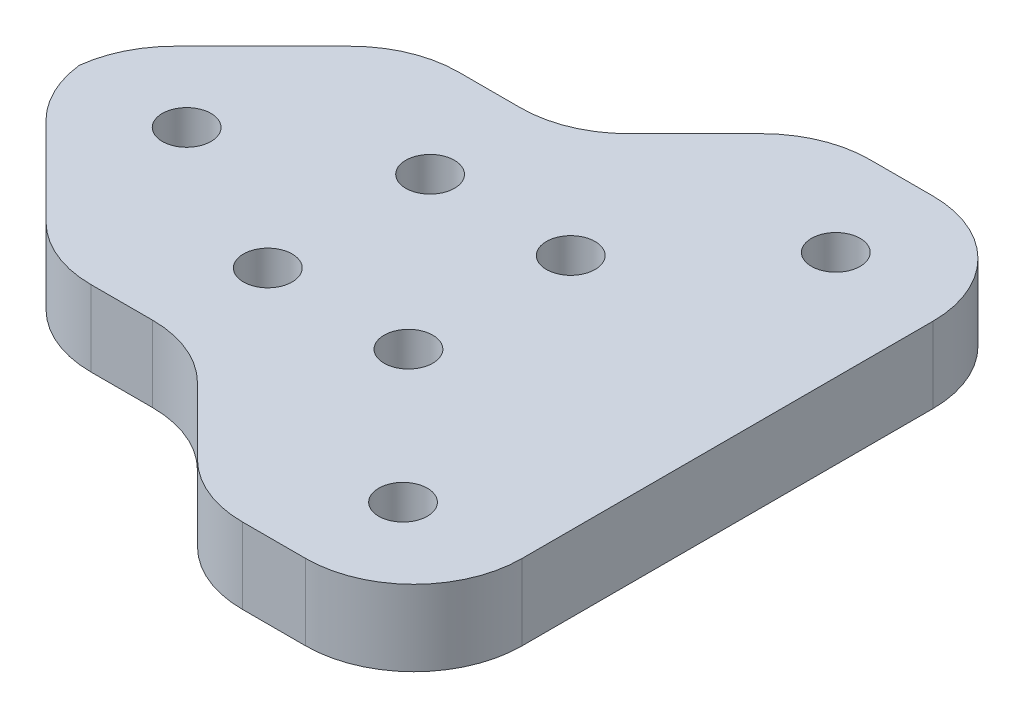
SolidWorks part; units mm, degrees
material "ABS"
ref_plane "Front Plane" through (0, 0, 0) normal (0, 0, 1) x (1, 0, 0)
ref_plane "Top Plane" through (0, 0, 0) normal (0, 1, 0) x (1, 0, 0)
ref_plane "Right Plane" through (0, 0, 0) normal (1, 0, 0) x (0, 0, -1)
sketch "Sketch1" plane through (0, 0, 0) normal (0, 1, 0) x (1, 0, 0)
  line L1 (0, 0) -> (60, 0)
  line L2 (0, 0) -> (0, 58)
  line L3 (0, 58) -> (60, 58)
  line L4 (60, 0) -> (60, 58)
  dimension "D1" = 58
  dimension "D2" = 60
extrude "Boss-Extrude1" add sketch "Sketch1" along normal blind 7
sketch "Sketch2" plane through (0, 0, 0) normal (0, 1, 0) x (1, 0, 0)
  line L0 (0, 58) -> (0, 0) construction
  line L1 (0, 7) -> (60, 7)
  line L2 (0, 7) -> (0, 0)
  line L3 (0, 0) -> (60, 0)
  line L4 (60, 7) -> (60, 0)
  dimension "D1" = 7
extrude "Boss-Extrude2" [suppressed] add sketch "Sketch2" against normal blind 20
hole_wizard "M4 Clearance Slot1" [suppressed] positions "Sketch3" profile "Sketch4" size "M4" standard "ANSI Metric"
sketch "Sketch3" plane through (0, 7, 0) normal (0, 1, 0) x (1, 0, 0)
  line L0 (32.05, 70) -> (32.05, 7) construction
  line L1 (64.1, 70) -> (0, 70) construction
  line L4 (16.235, 62.5) -> (47.865, 62.5) construction
  line L5 (47.865, 62.5) -> (47.865, 14.5) construction
  line L6 (47.865, 14.5) -> (16.235, 14.5) construction
  line L7 (16.235, 14.5) -> (16.235, 62.5) construction
  line L18 (40.365, 62.5) -> (55.365, 62.5) construction
  point P2 (47.865, 62.5)
  point P4 (47.865, 14.5)
  point P24 (16.235, 38.5)
  point P26 (32.05, 62.5)
  dimension "D1" = 31.63
  dimension "D2" = 48
  dimension "D3" = 15
  dimension "D4" = 31.5
sketch "Sketch4" plane through (47.865, 7, -62.5) normal (1, 0, 0) x (0, 0, 1)
  line L0 (0, 0) -> (0, 7)
  line L1 (0, 7) -> (2.25, 7)
  line L2 (2.25, 7) -> (2.25, 0)
  line L5 (2.25, 0) -> (0, 0)
  line L11 (0, -6.35) -> (0, 107.95) construction
  dimension "Thru Hole Dia." = 4.5
  dimension "Thru Hole Depth" = 7
hole_wizard "M2 Clearance Hole1" [suppressed] positions "Sketch8" profile "Sketch9" hole size "M2" standard "ANSI Metric"
sketch "Sketch8" plane through (0, 0, 0) normal (-1, 0, 0) x (0, 0, 1)
  line L4 (-29.5, 3.5) -> (-47.5, 3.5) construction
  line L7 (-70, 7) -> (-70, 0) construction
  point P0 (-47.5, 3.5)
  point P2 (-29.5, 3.5)
  point P23 (-70, 3.5)
  point P25 (-38.5, 3.5)
  dimension "D1" = 18
  dimension "D2" = 31.5
sketch "Sketch9" plane through (0, 3.5, -47.5) normal (0, 1, 0) x (0, 0, 1)
  line L0 (0, 0) -> (0, 35.721)
  line L1 (0, 35.721) -> (1.2, 35)
  line L2 (1.2, 35) -> (1.2, 0)
  line L5 (1.2, 0) -> (0, 0)
  line L10 (0, 35.721) -> (-1.2, 35) construction
  line L11 (0, -6.35) -> (0, 107.95) construction
  dimension "Hole Dia." = 2.4
  dimension "Hole Depth" = 35
  dimension "Drill Angle" = 118
sketch "Sketch11" plane through (0, 7, 0) normal (0, 1, 0) x (1, 0, 0)
  line L0 (0, 46) -> (28, 46)
  line L1 (0, 58) -> (0, 0) construction
  line L2 (28, 46) -> (40, 58)
  line L3 (60, 58) -> (0, 58) construction
  line L4 (0, 46) -> (0, 58)
  line L5 (0, 58) -> (40, 58)
  dimension "D1" = 135
  dimension "D2" = 12
  dimension "D3" = 40
extrude "Cut-Extrude2" [suppressed] cut sketch "Sketch11" against normal through all
sketch "Sketch12" [suppressed] plane through (0, 7, 0) normal (0, 1, 0) x (1, 0, 0)
  line L0 (18.475, 58) -> (18.475, 21.5)
  line L1 (0, 58) -> (28, 58) construction
  line L2 (18.475, 21.5) -> (0, 21.5)
  line L3 (0, 58) -> (0, 0) construction
  line L4 (0, 20.5) -> (19.475, 20.5)
  line L5 (19.475, 20.5) -> (19.475, 58)
  line L6 (19.475, 58) -> (18.475, 58)
  line L7 (0, 20.5) -> (0, 21.5)
  line L8 (0, 58) -> (0, 0) construction
  dimension "D3" = 18.475
  dimension "D1" = 1
  dimension "D2" = 1
  dimension "D4" = 36.5
extrude "Cut-Extrude3" [suppressed] cut sketch "Sketch12" against normal through all
sketch "Sketch13" [suppressed] plane through (0, 7, 0) normal (0, 1, 0) x (1, 0, 0)
  line L0 (19.475, 58) -> (28, 58) construction
  line L1 (24.475, 51.25) -> (27.975, 51.25)
  line L2 (24.475, 51.25) -> (24.475, 25)
  line L3 (24.475, 25) -> (27.975, 25)
  line L4 (27.975, 51.25) -> (27.975, 25)
  line L5 (19.475, 20.5) -> (19.475, 58) construction
  point P6 (26.225, 51.25)
  dimension "D1" = 3.5
  dimension "D2" = 26.25
  dimension "D3" = 5
  dimension "D4" = 6.75
extrude "Cut-Extrude4" [suppressed] cut sketch "Sketch13" against normal through all
sketch "Sketch14" [suppressed] plane through (64.1, 0, 0) normal (1, 0, 0) x (0, 0, -1)
  line L0 (70, 0) -> (7, -20)
  line L1 (7, -20) -> (7, 0)
  line L2 (7, 0) -> (70, 0)
extrude "Boss-Extrude3" [suppressed] add sketch "Sketch14" against normal blind 3
sketch "Sketch15" [suppressed] plane through (0, 0, 0) normal (-1, 0, 0) x (0, 0, 1)
  line L0 (-19.5, 0) -> (-7, -20)
  line L1 (-7, -20) -> (-7, 0)
  line L2 (-7, 0) -> (-19.5, 0)
extrude "Boss-Extrude4" [suppressed] add sketch "Sketch15" against normal blind 3
ref_plane "Plane1" [suppressed] through (28, 0, 0) normal (1, 0, 0) x (0, 0, -1)
sketch "Sketch16" [suppressed] plane through (28, 0, 0) normal (1, 0, 0) x (0, 0, -1)
  line L0 (58, 0) -> (7, 0)
  line L1 (7, 0) -> (7, -20)
  line L2 (7, -20) -> (58, 0)
extrude "Boss-Extrude5" [suppressed] add sketch "Sketch16" against normal blind 3
hole_wizard "M4 Clearance Hole1" [suppressed] positions "Sketch17" profile "Sketch18" hole size "M4" standard "ANSI Metric"
sketch "Sketch17" [suppressed] plane through (0, 0, -7) normal (0, 0, -1) x (-1, 0, 0)
  line L0 (-61.1, -11.5) -> (-3, -11.5) construction
  line L1 (-61.1, 0) -> (-61.1, -20) construction
  line L2 (-3, -20) -> (-3, 0) construction
  line L4 (-61.1, -20) -> (-28, -20) construction
  line L5 (-25, 0) -> (-25, -20) construction
  point P0 (-51.1, -11.5)
  point P2 (-36.1, -11.5)
  point P4 (-17, -11.5)
  point P6 (-7, -11.5)
  dimension "D1" = 8.5
  dimension "D2" = 10
  dimension "D3" = 15
  dimension "D4" = 8
  dimension "D5" = 10
sketch "Sketch18" plane through (51.1, -11.5, -7) normal (1, 0, 0) x (0, 1, 0)
  line L0 (0, 0) -> (0, 7)
  line L1 (0, 7) -> (2.25, 7)
  line L2 (2.25, 7) -> (2.25, 0)
  line L5 (2.25, 0) -> (0, 0)
  line L11 (0, -6.35) -> (0, 107.95) construction
  dimension "Thru Hole Dia." = 4.5
  dimension "Thru Hole Depth" = 7
fillet "Fillet1" [suppressed] radius 10
fillet "Fillet2" [suppressed] radius 2
sketch "Sketch19" plane through (0, 0, 0) normal (0, 0, 1) x (1, 0, 0)
  line L1 (60, 7) -> (0, 7)
  line L2 (60, 7) -> (60, 0)
  line L3 (60, 0) -> (0, 0)
  line L4 (0, 7) -> (0, 0)
hole_wizard "M4 Clearance Hole2" positions "Sketch20" profile "Sketch21" hole size "M4" standard "ANSI Metric" end condition through all
sketch "Sketch20" plane through (0, 0, 0) normal (0, -1, 0) x (-1, 0, 0)
  line L0 (-25, 36.5) -> (-25, 21.5) construction
  line L2 (-25, 29) -> (0, 29) construction
  line L3 (0, 58) -> (0, 0) construction
  line L6 (-60, 58) -> (0, 58) construction
  point P0 (-25, 36.5)
  point P2 (-25, 21.5)
  dimension "D1" = 15
  dimension "D2" = 25
  dimension "D3" = 29
sketch "Sketch21" plane through (25, 0, -36.5) normal (1, 0, 0) x (0, 0, -1)
  line L0 (0, 0) -> (0, 7)
  line L1 (0, 7) -> (2.25, 7)
  line L2 (2.25, 7) -> (2.25, 0)
  line L5 (2.25, 0) -> (0, 0)
  line L11 (0, -6.35) -> (0, 107.95) construction
  dimension "Thru Hole Dia." = 4.5
  dimension "Thru Hole Depth" = 7
sketch "Sketch22" [suppressed] plane through (0, 0, 0) normal (0, -1, 0) x (1, 0, 0)
  line L0 (19.475, -58) -> (36.975, -58)
  line L1 (36.975, -58) -> (36.975, -20.5)
  line L2 (36.975, -20.5) -> (19.475, -20.5)
  line L3 (19.475, -20.5) -> (19.475, -58)
  line L4 (27.975, -51.25) -> (24.475, -51.25)
  line L5 (24.475, -51.25) -> (24.475, -25)
  line L6 (24.475, -25) -> (27.975, -25)
  line L7 (27.975, -25) -> (27.975, -51.25)
  dimension "D1" = 17.5
extrude "Boss-Extrude7" [suppressed] add sketch "Sketch22" along normal blind 4
hole_wizard "M4 Clearance Hole3" [suppressed] positions "Sketch23" profile "Sketch24" hole size "M4" standard "ANSI Metric"
sketch "Sketch23" [suppressed] plane through (19.475, 0, 0) normal (-1, 0, 0) x (0, 0, 1)
  line L0 (-58, 1.5) -> (-20.5, 1.5) construction
  line L1 (-58, -4) -> (-58, 7) construction
  line L2 (-20.5, 0) -> (-20.5, 7) construction
  point P0 (-47.5, 1.5)
  point P2 (-29.5, 1.5)
  dimension "D1" = 10.5
  dimension "D2" = 18
sketch "Sketch24" plane through (19.475, 1.5, -47.5) normal (0, 1, 0) x (0, 0, 1)
  line L0 (0, 0) -> (0, 15.8819)
  line L1 (0, 15.8819) -> (2.25, 14.53)
  line L2 (2.25, 14.53) -> (2.25, 0)
  line L5 (2.25, 0) -> (0, 0)
  line L10 (0, 15.8819) -> (-2.25, 14.53) construction
  line L11 (0, -6.35) -> (0, 107.95) construction
  dimension "Hole Dia." = 4.5
  dimension "Hole Depth" = 14.53
  dimension "Drill Angle" = 118
pattern_linear "LPattern1" count 2 spacing 13 along (1, 0, 0) of "M4 Clearance Hole2"
hole_wizard "M4 Clearance Hole4" positions "Sketch27" profile "Sketch28" hole size "M4" standard "ANSI Metric" end condition through all
sketch "Sketch27" plane through (0, 0, 0) normal (0, -1, 0) x (-1, 0, 0)
  line L0 (-30, 0) -> (-30, 58) construction
  line L2 (-60, 58) -> (0, 58) construction
  line L4 (-50, 9) -> (-50, 49) construction
  line L6 (-10, 29) -> (-50, 29) construction
  line L7 (0, 0) -> (-60, 0) construction
  line L8 (-60, 0) -> (-60, 58) construction
  line L9 (-10, 29) -> (0, 29) construction
  line L10 (0, 58) -> (0, 0) construction
  point P0 (-50, 49)
  point P2 (-50, 9)
  point P4 (-10, 29)
  point P21 (-30, 29)
  dimension "D1" = 40
  dimension "D2" = 40
sketch "Sketch28" plane through (50, 0, -49) normal (1, 0, 0) x (0, 0, -1)
  line L0 (0, 0) -> (0, 7)
  line L1 (0, 7) -> (2.25, 7)
  line L2 (2.25, 7) -> (2.25, 0)
  line L5 (2.25, 0) -> (0, 0)
  line L11 (0, -6.35) -> (0, 107.95) construction
  dimension "Thru Hole Dia." = 4.5
  dimension "Thru Hole Depth" = 7
sketch "Sketch29" plane through (0, 0, 0) normal (0, -1, 0) x (1, 0, 0)
  line L0 (40, 0) -> (28, -12)
  line L1 (0, 0) -> (60, 0) construction
  line L2 (28, -12) -> (14, -12)
  line L3 (14, -12) -> (0, -26)
  line L4 (0, -58) -> (0, 0) construction
  line L5 (0, -29) -> (60, -29) construction
  line L6 (60, 0) -> (60, -58) construction
  line L7 (0, -26) -> (0, 0)
  line L8 (0, 0) -> (40, 0)
  line L9 (0, -32) -> (0, -58)
  line L10 (14, -46) -> (0, -32)
  line L11 (28, -46) -> (14, -46)
  line L12 (0, -58) -> (40, -58)
  line L13 (40, -58) -> (28, -46)
  dimension "D1" = 14
  dimension "D2" = 45
  dimension "D3" = 6
  dimension "D4" = 12
extrude "Cut-Extrude5" cut sketch "Sketch29" against normal through all
fillet "Fillet3" radius 10 10 edges at (60, 3.5, 0) (60, 3.5, -58) (40, 3.5, -58) (28, 3.5, -46) (14, 3.5, -46) (0, 3.5, -32) (0, 3.5, -26) (14, 3.5, -12) (40, 3.5, 0) (28, 3.5, -12)
